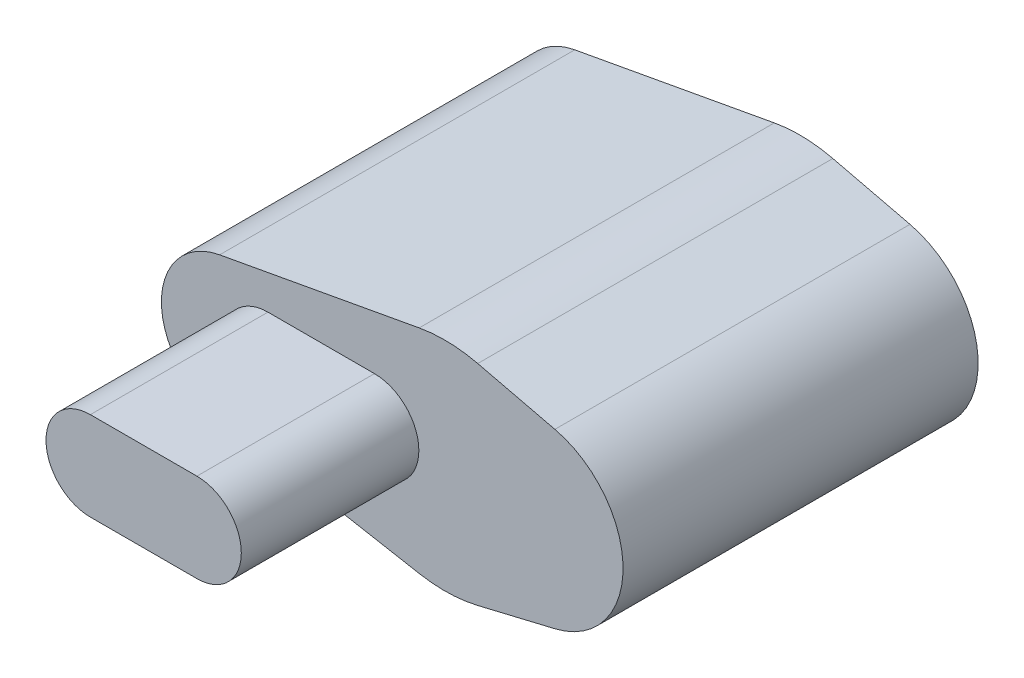
SolidWorks part; units mm, degrees
ref_plane "前视基准面" through (0, 0, 0) normal (0, 0, 1) x (1, 0, 0)
ref_plane "上视基准面" through (0, 0, 0) normal (0, 1, 0) x (1, 0, 0)
ref_plane "右视基准面" through (0, 0, 0) normal (1, 0, 0) x (0, 0, -1)
sketch "草图1" plane through (0, 0, 0) normal (0, 0, 1) x (1, 0, 0)
  line L0 (0, 0) -> (-150, 0) construction
  line L1 (0, 50) -> (-48.2362, 62.9248)
  line L2 (0, 50) -> (-126.1623, 50)
  line L3 (-150, 0) -> (-170, 0)
  line L4 (-170, 40) -> (-48.2362, 62.9248)
  line L5 (-48.2362, 62.9248) -> (11.6136, 48.6325)
  line L6 (-48.2362, 62.9248) -> (-177.1939, 39.3478)
  line L7 (-48.2362, -62.9248) -> (11.6136, -48.6325)
  line L8 (-48.2362, -62.9248) -> (-177.1939, -39.3478)
  circle A0 centre (0, 0) radius 25
  circle A1 centre (0, 0) radius 50
  circle A3 centre (-170, 0) radius 40
  dimension "D1" = 15
  dimension "D2" = 150
extrude "凸台-拉伸1" add sketch "草图1" along normal blind 200 contours A3 | L0 A1 L2 L4 A3 | L4 L2 L1 | A0 A1 | A0 | A1 L0 A3 L8 L7 | A3 L4 L2 L6 | A1 L5 L1 | L4 L6 L2 region at (-34.3553, 34.3553, 0) region at (-84.7196, -31.1499, 0) region at (-89.3631, 27.3432, 0) region at (0, 24.2929, 0) region at (-145.1096, -29.8536, 0) region at (-55.0406, 54.3083, 0) region at (-13.4323, 54.1513, 0) region at (-147.7278, 44.4709, 0) region at (-94.684, 54.3083, 0)
fillet "圆角1" radius 80 2 edges at (-48.2362, -62.9248, 100) (-48.2362, 62.9248, 100)
sketch "草图2" plane through (0, 0, 200) normal (0, 0, 1) x (1, 0, 0)
  line L0 (0, 0) -> (-120, 0) construction
  line L2 (-150, 25) -> (-90, 25)
  line L3 (-150, 25) -> (-150, -25)
  line L4 (-150, -25) -> (-90, -25)
  line L5 (-90, 25) -> (-90, -25)
  line L6 (-150, 25) -> (-90, -25) construction
  line L7 (-150, -25) -> (-90, 25) construction
  circle A0 centre (-90, 0) radius 25
  circle A1 centre (-150, 0) radius 25
  dimension "D1" = 120
  dimension "D2" = 50
  dimension "D3" = 60
extrude "凸台-拉伸2" add sketch "草图2" along normal blind 100 contours L3 A1 | L3 A1 | A1 L4 A0 L2 | L5 A0 | L5 A0 region at (-139.3897, 0, 200) region at (-120, 0, 200) region at (-160.6103, 0, 200) region at (-79.3897, 0, 200) region at (-100.6103, 0, 200)
sketch "草图3" plane through (0, 0, 0) normal (0, 0, -1) x (-1, 0, 0)
  circle A0 centre (0, 0) radius 25
extrude "切除-拉伸1" cut sketch "草图3" against normal blind 160
sketch "草图4" plane through (0, 0, 0) normal (0, 0, -1) x (-1, 0, 0)
  line L0 (0, 0) -> (150, 0) construction
  circle A0 centre (150, 0) radius 25
  dimension "D1" = 150
extrude "凸台-拉伸3" add sketch "草图4" along normal blind 12
sketch "草图5" plane through (0, 0, -12) normal (0, 0, -1) x (-1, 0, 0)
  circle A0 centre (150, 0) radius 28
extrude "凸台-拉伸4" add sketch "草图5" along normal blind 4
sketch "草图6" plane through (0, 0, -16) normal (0, 0, -1) x (-1, 0, 0)
  circle A0 centre (150, 0) radius 20
extrude "凸台-拉伸5" add sketch "草图6" along normal blind 10
chamfer "倒角1" distance 10 distance2 5 1 edges at (-170, 0, -26) first distance on face at (-170, 0, -26)
sketch "草图7" plane through (0, 0, -26) normal (0, 0, -1) x (-1, 0, 0)
  circle A0 centre (150, 0) radius 7
extrude "切除-拉伸2" cut sketch "草图7" against normal blind 200
